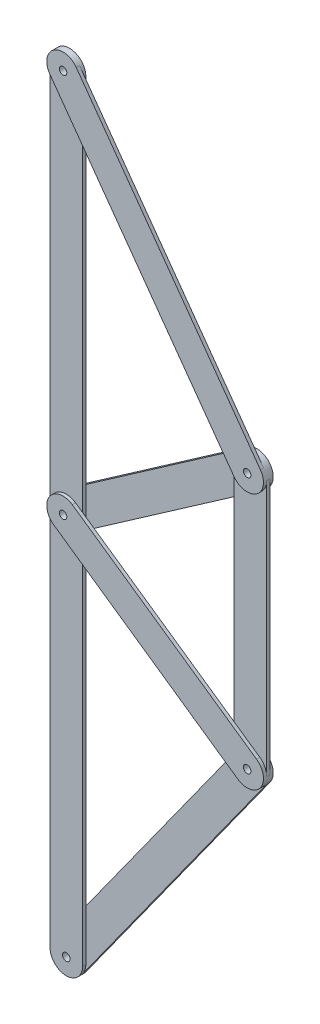
SolidWorks part; units mm, degrees
note: The reader was unsure of these and kept them because the rebuilt part matched: shared geometry of "Sketch1<4>", "Sketch1<5>", "Sketch1<6>".
material "AISI 1020"
ref_plane "Front Plane" through (0, 0, 0) normal (1, 0, 0) x (0, 1, 0)
ref_plane "Top Plane" through (0, 0, 0) normal (0, 0, 1) x (0, 1, 0)
ref_plane "Right Plane" through (0, 0, 0) normal (0, 1, 0) x (-1, 0, 0)
sketch "Sketch1" plane through (0, 0, 0) normal (0, 0, 1) x (0, 1, 0)
  line L0 (-354.9214, 254.9213) -> (0, 0) construction
  line L1 (-341.7727, 273.228) -> (13.1487, 18.3066)
  line L2 (-368.07, 236.6147) -> (-13.1487, -18.3066)
  line L3 (-354.9214, 254.9213) -> (177.4607, 254.9213) construction
  line L4 (-354.9214, 277.4607) -> (177.4607, 277.4607)
  line L5 (-354.9214, 232.382) -> (177.4607, 232.382)
  line L6 (0, 0) -> (354.9214, 0) construction
  line L7 (0, 22.5393) -> (354.9214, 22.5393)
  line L8 (0, -22.5393) -> (354.9214, -22.5393)
  line L9 (177.4607, 254.9213) -> (709.8427, 254.9213) construction
  line L10 (177.4607, 277.4607) -> (709.8427, 277.4607)
  line L11 (177.4607, 232.382) -> (709.8427, 232.382)
  line L12 (177.4607, 254.9213) -> (354.9214, 0) construction
  line L13 (195.9591, 267.7988) -> (373.4198, 12.8775)
  line L14 (158.9622, 242.0439) -> (336.4229, -12.8775)
  line L15 (177.4607, 254.9213) -> (0, 0) construction
  line L16 (195.9591, 242.0439) -> (18.4984, -12.8775)
  line L17 (158.9622, 267.7988) -> (-18.4984, 12.8775)
  line L18 (709.8427, 254.9213) -> (354.9214, 0) construction
  line L19 (722.9914, 236.6147) -> (368.07, -18.3066)
  line L20 (696.694, 273.228) -> (341.7727, 18.3066)
  arc A3 (-341.7727, 273.228) -> (-368.07, 236.6147) centre (-354.9214, 254.9213) ccw
  arc A4 (-13.1487, -18.3066) -> (13.1487, 18.3066) centre (0, 0) ccw
  arc A5 (-354.9214, 277.4607) -> (-354.9214, 232.382) centre (-354.9214, 254.9213) ccw
  arc A6 (177.4607, 232.382) -> (177.4607, 277.4607) centre (177.4607, 254.9213) ccw
  arc A7 (0, 22.5393) -> (0, -22.5393) centre (0, 0) ccw
  arc A8 (354.9214, -22.5393) -> (354.9214, 22.5393) centre (354.9214, 0) ccw
  arc A9 (177.4607, 277.4607) -> (177.4607, 232.382) centre (177.4607, 254.9213) ccw
  arc A10 (709.8427, 232.382) -> (709.8427, 277.4607) centre (709.8427, 254.9213) ccw
  arc A11 (195.9591, 267.7988) -> (158.9622, 242.0439) centre (177.4607, 254.9213) ccw
  arc A12 (336.4229, -12.8775) -> (373.4198, 12.8775) centre (354.9214, 0) ccw
  arc A13 (195.9591, 242.0439) -> (158.9622, 267.7988) centre (177.4607, 254.9213) ccw
  arc A14 (-18.4984, 12.8775) -> (18.4984, -12.8775) centre (0, 0) ccw
  arc A15 (722.9914, 236.6147) -> (696.694, 273.228) centre (709.8427, 254.9213) ccw
  arc A16 (341.7727, 18.3066) -> (368.07, -18.3066) centre (354.9214, 0) ccw
  point P2 (166.9555, 260.4365)
  point P3 (-177.4607, 127.4607)
  point P8 (-88.7303, 254.9213)
  point P15 (177.4607, 0)
  point P23 (443.6517, 254.9213)
  point P30 (266.191, 127.4607)
  point P37 (88.7303, 127.4607)
  point P44 (532.382, 127.4607)
  point P51 (0, 0)
  point P52 (0, 0)
  point P53 (0, 0)
  point P54 (340.0021, 150.2191)
  point P55 (299.014, 194.1435)
  point P56 (341.1732, 151.9757)
  point P57 (0, 0)
  point P58 (-214.5095, 253.2751)
  point P59 (0, 0)
  point P60 (0, 0)
  point P61 (0, 0)
  point P62 (0, 0)
  point P63 (0, 0)
  point P64 (131.5479, 257.3739)
  point P65 (215.3187, 273.1868)
  point P66 (606.6209, 304.8427)
  dimension "D1" = 45.0787
  dimension "D2" = 45.0787
  dimension "D3" = 45.0787
  dimension "D4" = 45.0787
  dimension "D5" = 45.0787
  dimension "D6" = 45.0787
  dimension "D7" = 45.0787
  dimension "D8" = 354.9214
  dimension "D9" = 254.9213
  dimension "D10" = 354.9214
extrude "CD" add sketch "Sketch1" along normal blind 4.5079 contours L8 A8 L7 A7
extrude "BE & AE" add sketch "Sketch1<4>" along normal blind 4.5079 separate body contours L5 A6 L4 A5 | L11 A10 L10 A9
sketch "Sketch1<4>" plane through (0, 0, 0) normal (0, 0, 1) x (0, 1, 0) same geometry as "Sketch1"
extrude "Boss-Extrude3" add sketch "Sketch1<5>" against normal blind 4.5079 contours L2 A4 L1 A3
sketch "Sketch1<5>" plane through (0, 0, 0) normal (0, 0, 1) x (0, 1, 0) same geometry as "Sketch1"
sketch "Sketch3" plane through (0, 0, 4.5079) normal (0, 0, 1) x (1, 0, 0)
  line L0 (-254.9213, 177.4607) -> (0, 0) construction
  line L1 (-242.0439, 195.9591) -> (12.8775, 18.4984)
  line L2 (-267.7988, 158.9622) -> (-12.8775, -18.4984)
  line L3 (-267.7988, 158.9622) -> (-12.8775, -18.4984) construction
  line L4 (-267.7988, 158.9622) -> (-12.8775, -18.4984)
  line L5 (-242.0439, 195.9591) -> (12.8775, 18.4984) construction
  arc A0 (-242.0439, 195.9591) -> (-267.7988, 158.9622) centre (-254.9213, 177.4607) ccw
  arc A1 (-12.8775, -18.4984) -> (12.8775, 18.4984) centre (0, 0) ccw
  point P4 (-127.4607, 88.7303)
  dimension "D1" = 45.0787
  dimension "D2" = 45.0787
extrude "Boss-Extrude4" add sketch "Sketch3" along normal blind 4.5079
extrude "Boss-Extrude5" add sketch "Sketch1<6>" against normal blind 4.5079 contours L14 A12 L13 A11
sketch "Sketch1<6>" plane through (0, 0, 0) normal (0, 0, 1) x (0, 1, 0) same geometry as "Sketch1"
sketch "Sketch4" plane through (0, 0, 4.5079) normal (0, 0, 1) x (1, 0, 0)
  line L0 (-254.9213, 709.8427) -> (0, 354.9213) construction
  line L1 (-236.6147, 722.9914) -> (18.3066, 368.07)
  line L2 (-273.228, 696.694) -> (-18.3066, 341.7727)
  arc A0 (-236.6147, 722.9914) -> (-273.228, 696.694) centre (-254.9213, 709.8427) ccw
  arc A1 (-18.3066, 341.7727) -> (18.3066, 368.07) centre (0, 354.9213) ccw
  point P4 (-127.4607, 532.382)
  dimension "D1" = 45.0787
extrude "Boss-Extrude7" add sketch "Sketch4" along normal blind 4.5079
sketch "Sketch5" plane through (0, 0, 9.0157) normal (0, 0, 1) x (1, 0, 0)
  circle A0 centre (0, 0) radius 5.2112
  circle A1 centre (-254.9213, 177.4607) radius 5.2112
  circle A2 centre (-254.9213, -354.9214) radius 5.2112
  circle A3 centre (0, 354.9214) radius 5.2112
  circle A4 centre (-254.9213, 709.8427) radius 5.2112
  point P0 (0, 0)
  dimension "D1" = 10.4224
extrude "Cut-Extrude1" cut sketch "Sketch5" against normal through all both and the other way through all
